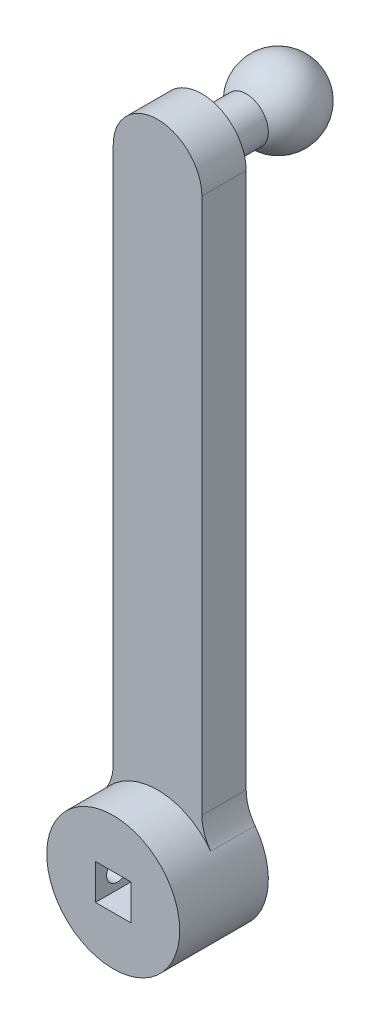
SolidWorks part; units mm, degrees
material "ASTM A36 Steel"
ref_plane "Front Plane" through (0, 0, 0) normal (0, 0, 1) x (1, 0, 0)
ref_plane "Top Plane" through (0, 0, 0) normal (0, 1, 0) x (1, 0, 0)
ref_plane "Right Plane" through (0, 0, 0) normal (1, 0, 0) x (0, 0, -1)
sketch "Sketch1" plane through (0, 0, 0) normal (0, 0, 1) x (1, 0, 0)
  line L1 (-2.54, -2.54) -> (2.54, -2.54) construction
  line L2 (-2.54, -2.54) -> (-2.54, 2.54) construction
  line L3 (-2.54, 2.54) -> (2.54, 2.54) construction
  line L4 (2.54, -2.54) -> (2.54, 2.54) construction
  line L5 (-2.54, -2.54) -> (2.54, 2.54) construction
  line L6 (-2.54, 2.54) -> (2.54, -2.54) construction
  circle A0 centre (0, 0) radius 9.525
  point P0 (0, 0)
  dimension "D3" = 19.05
  dimension "D1" = 5.08
  dimension "D2" = 5.08
extrude "Boss-Extrude1" add sketch "Sketch1" along normal blind 12.7
sketch "Sketch2" plane through (0, 0, 12.7) normal (0, 0, 1) x (1, 0, 0)
  line L0 (-2.54, -2.54) -> (-2.54, 2.54) construction
  line L1 (-2.54, -2.54) -> (2.54, -2.54) construction
  line L2 (2.54, -2.54) -> (2.54, 2.54) construction
  line L3 (-2.54, 2.54) -> (2.54, 2.54) construction
  line L4 (-2.54, -2.54) -> (-2.54, 2.54)
  line L5 (-2.54, -2.54) -> (2.54, -2.54)
  line L6 (2.54, -2.54) -> (2.54, 2.54)
  line L7 (-2.54, 2.54) -> (2.54, 2.54)
  circle A1 centre (0, 0) radius 9.525
  circle A2 centre (0, 0) radius 9.525
  dimension "D2" = 5.08
  dimension "D1" = 0
extrude "Cut-Extrude2" cut sketch "Sketch2" against normal blind 6.35 contours L7 L4 L5 L6 region at (0, 0, 12.7)
sketch "Sketch3" plane through (0, 0, 0) normal (0, 0, -1) x (-1, 0, 0)
  line L1 (-6.35, 10.1721) -> (-6.35, 7.0995)
  line L2 (-6.35, 10.1721) -> (-6.35, 86.3721)
  line L3 (6.35, 10.1721) -> (6.35, 86.3721)
  line L4 (-6.35, 7.0995) -> (6.35, 7.0995)
  line L5 (6.35, 7.0995) -> (6.35, 10.1721)
  arc A3 (6.35, 86.3721) -> (-6.35, 86.3721) centre (0, 86.3721) ccw
  circle A4 centre (0, 0) radius 9.525 construction
  dimension "D3" = 76.2
  dimension "D4" = 76.2
extrude "Boss-Extrude2" add sketch "Sketch3" against normal blind 6.35
sketch "Sketch4" plane through (0, 0, 0) normal (0, 0, -1) x (-1, 0, 0)
  circle A0 centre (0, 86.3721) radius 3.175
  dimension "D1" = 6.35
fillet "Fillet2" radius 6.35 2 edges at (-6.35, 7.0995, 3.175) (6.35, 7.0995, 3.175)
sketch "Sketch5" plane through (2.54, 0, 0) normal (-1, 0, 0) x (0, 0, 1)
  line L2 (12.7, -9.525) -> (12.7, 9.525) construction
  circle A1 centre (9.525, 0) radius 1.5875
  dimension "D1" = 3.175
  dimension "D2" = 3.175
extrude "Cut-Extrude3" cut sketch "Sketch5" along normal up to surface (12.065 mm away) up to face at (9.525, 0, 12.7)
extrude "Boss-Extrude3" add sketch "Sketch4" along normal blind 6.35
dome "Dome1" faces to dome 1 distance 10.16 reverse direction no elliptical dome no face at (-3.175, 86.3721, -6.35) parameters "D1"=10.16
